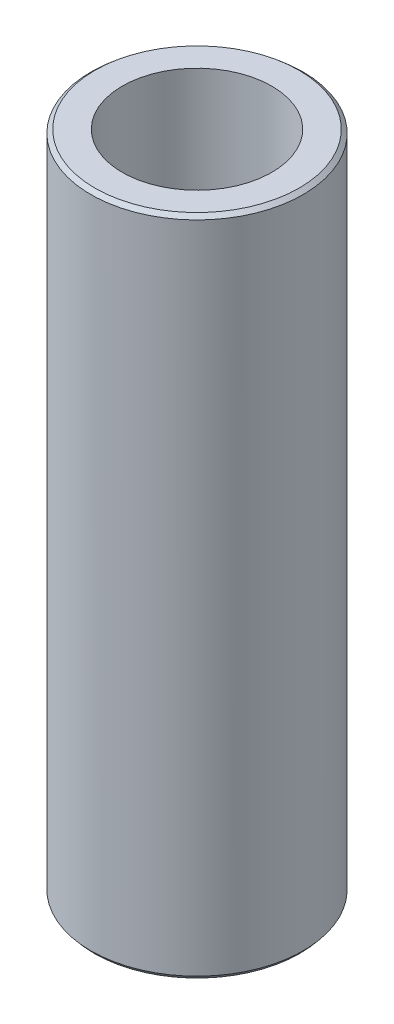
SolidWorks part; units mm, degrees
ref_plane "Front Plane" through (0, 0, 0) normal (0, 0, 1) x (1, 0, 0)
ref_plane "Top Plane" through (0, 0, 0) normal (0, 1, 0) x (1, 0, 0)
ref_plane "Right Plane" through (0, 0, 0) normal (1, 0, 0) x (0, 0, -1)
sketch "Sketch1" plane through (0, 0, 0) normal (0, 1, 0) x (1, 0, 0)
  circle A0 centre (0, 0) radius 40
  dimension "SHAFT_OD" = 80
extrude "Boss-Extrude1" add sketch "Sketch1" along normal blind 249.5635
sketch "Sketch2" plane through (0, 0, 0) normal (0, 1, 0) x (1, 0, 0)
  circle A0 centre (0, 0) radius 28.1654
  dimension "BORE_D" = 56.3308
extrude "Cut-Extrude1" cut sketch "Sketch2" along normal through all
chamfer "Chamfer1" distance 1.3199 angle 49.647 2 edges at (0, 249.5635, 40) (0, 0, 40) first distance on face at (0, 249.5635, 40) first distance on face at (0, 0, 28.1654)
